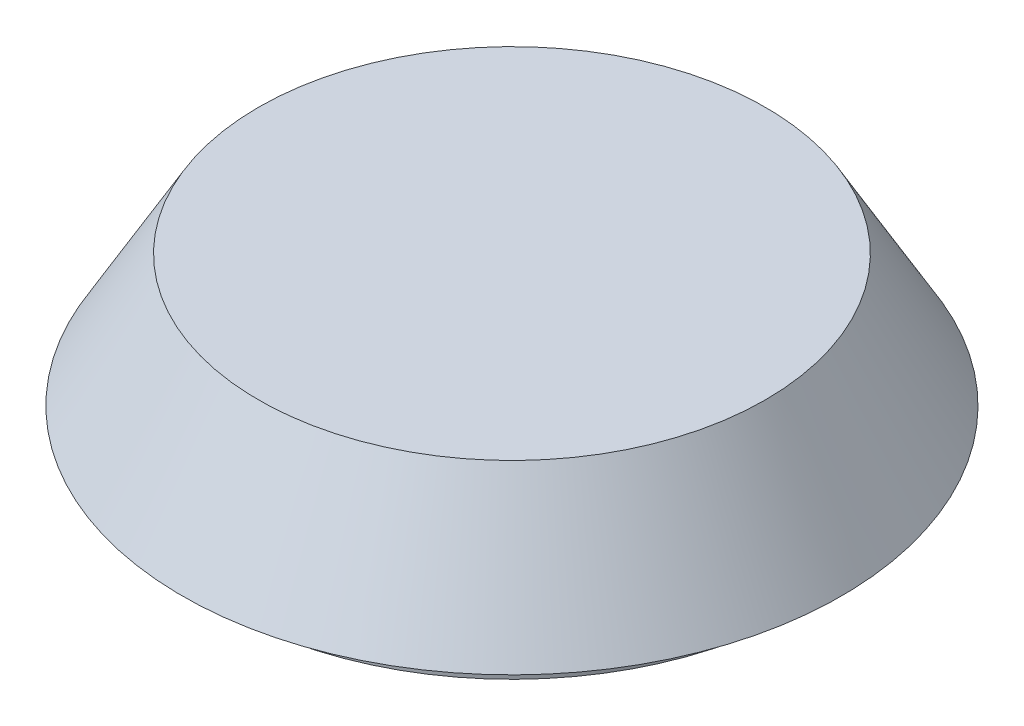
SolidWorks part; units mm, degrees
ref_plane "Front Plane" through (0, 0, 0) normal (0, 0, 1) x (1, 0, 0)
ref_plane "Top Plane" through (0, 0, 0) normal (0, 1, 0) x (1, 0, 0)
ref_plane "Right Plane" through (0, 0, 0) normal (1, 0, 0) x (0, 0, -1)
sketch "Sketch2" plane through (0, 0, 0) normal (0, 1, 0) x (1, 0, 0)
  circle A0 centre (0, 0) radius 43.85
  dimension "D1" = 87.7
extrude "Boss-Extrude1" add sketch "Sketch2" against normal blind 5 draft 1
sketch "Sketch4" plane through (0, 0, 0) normal (0, 0, 1) x (1, 0, 0)
  line L0 (0, 0) -> (50, 0)
  line L1 (50, 0) -> (38.453, 20)
  line L2 (38.453, 20) -> (0, 20)
  line L3 (0, 20) -> (0, 0)
  line L7 (48.235, 0) -> (-48.235, 0) construction
  dimension "D1" = 50
  dimension "D2" = 60
  dimension "D3" = 20
  dimension "D4" = 0
revolve "Revolve1" add sketch "Sketch4" angle 360 about L3
equation "\"D1@Sketch2\"=87.7"
